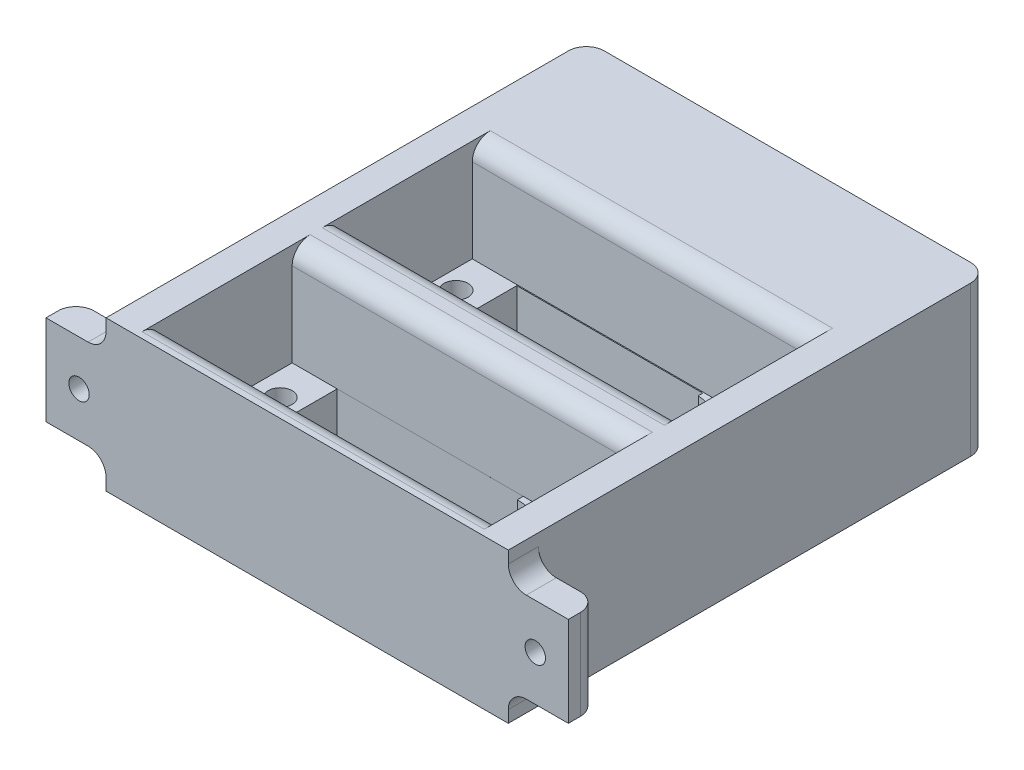
SolidWorks part; units mm, degrees
note: The reader was unsure of these and kept them because the rebuilt part matched: shared geometry of "Sketch4<2>".
ref_plane "Front Plane" through (0, 0, 0) normal (0, 0, 1) x (1, 0, 0)
ref_plane "Top Plane" through (0, 0, 0) normal (0, 1, 0) x (1, 0, 0)
ref_plane "Right Plane" through (0, 0, 0) normal (1, 0, 0) x (0, 0, -1)
sketch "Sketch1" plane through (0, 0, 0) normal (0, 1, 0) x (1, 0, 0)
  line L1 (-33.5, 15) -> (33.5, 15)
  line L2 (-33.5, 15) -> (-33.5, -15)
  line L3 (-33.5, -15) -> (33.5, -15)
  line L4 (33.5, 15) -> (33.5, -15)
  line L5 (-33.5, 15) -> (33.5, -15) construction
  line L6 (-33.5, -15) -> (33.5, 15) construction
  point P0 (0, 0)
  dimension "D1" = 67
  dimension "D2" = 30
extrude "Boss-Extrude1" add sketch "Sketch1" along normal blind 25
sketch "Sketch2" plane through (0, 25, 0) normal (0, 1, 0) x (1, 0, 0)
  line L1 (-28.5, 11) -> (28.5, 11)
  line L2 (-28.5, 11) -> (-28.5, -11)
  line L3 (-28.5, -11) -> (28.5, -11)
  line L4 (28.5, 11) -> (28.5, -11)
  line L5 (-28.5, 11) -> (28.5, -11) construction
  line L6 (-28.5, -11) -> (28.5, 11) construction
  point P0 (0, 0)
  dimension "D1" = 22
  dimension "D2" = 57
extrude "Cut-Extrude1" cut sketch "Sketch2" against normal blind 17
sketch "Sketch3" plane through (0, 8, 0) normal (0, 1, 0) x (1, 0, 0)
  line L0 (-36.7154, 0) -> (36.0411, 0) construction
  line L1 (24.5, -19.9745) -> (24.5, 16.1003) construction
  line L2 (-24.5, -21.1882) -> (-24.5, 16.1003) construction
  circle A0 centre (24.5, 5) radius 2
  circle A1 centre (24.5, -5) radius 2
  circle A2 centre (-24.5, 5) radius 2
  circle A3 centre (-24.5, -5) radius 2
  circle A4 centre (10, 0) radius 10
  circle A5 centre (-3, 0) radius 8
  dimension "D2" = 4
  dimension "D3" = 5
  dimension "D4" = 5
  dimension "D5" = 20
  dimension "D6" = 14.5
  dimension "D7" = 27.5
  dimension "D9" = 16
  dimension "D1" = 49
  dimension "D8" = 10
extrude "Cut-Extrude2" cut sketch "Sketch3" against normal up to surface (8 mm away) contours A4 A5 | A5 A4 | A2 | A3 | A0 | A1 up to face at (0, 0, 0)
sketch "Sketch4" plane through (33.5, 0, 0) normal (1, 0, 0) x (0, 0, -1)
  line L0 (-15, 25) -> (-15, 0) construction
  line L1 (-15, 20) -> (-10, 20)
  line L2 (-15, 20) -> (-15, 5)
  line L3 (-15, 5) -> (-10, 5)
  line L4 (-10, 20) -> (-10, 5)
  line L5 (-15, 20) -> (-10, 5) construction
  line L6 (-15, 5) -> (-10, 20) construction
  point P0 (-12.5, 12.5)
  dimension "D1" = 5
  dimension "D2" = 0
  dimension "D3" = 12.5
  dimension "D4" = 15
extrude "Boss-Extrude2" add sketch "Sketch4" against normal blind 10 from surface at -67 starting at face at (-33.5, 12.5, 0)
extrude "Boss-Extrude3" add sketch "Sketch4<2>" along normal blind 10
sketch "Sketch4<2>" plane through (33.5, 0, 0) normal (1, 0, 0) x (0, 0, -1) same geometry as "Sketch4"
sketch "Sketch5" plane through (0, 0, 10) normal (0, 0, -1) x (-1, 0, 0)
  circle A0 centre (38, 12.5) radius 1.7
  circle A1 centre (-38, 12.5) radius 1.7
  dimension "D1" = 3.4
  dimension "D2" = 12.5
  dimension "D3" = 38
  dimension "D4" = 38
extrude "Cut-Extrude3" cut sketch "Sketch5" against normal blind 10
sketch "Sketch6" plane through (0, 8, 0) normal (0, 1, 0) x (1, 0, 0)
  line L0 (-21, 11.0046) -> (-21.0033, -10.9975)
  line L1 (-21.0033, -10.9975) -> (10, -11.0022)
  line L3 (10, -11.0022) -> (10, 10.9978)
  line L4 (10, 10.9978) -> (-21, 11.0046)
  dimension "D1" = 31
  dimension "D2" = 22
  dimension "D3" = 11
  dimension "D4" = 10
extrude "Cut-Extrude4" cut sketch "Sketch6" against normal up to surface (8 mm away) up to face at (24.5, 0, 7)
sketch "Sketch7" plane through (0, 0, 15) normal (0, 0, 1) x (1, 0, 0)
  line L0 (7.3795, -4.5) -> (7.3795, -8.1) construction
  line L1 (-32.6205, 4.2383) -> (-210.3795, 4.2383)
  line L2 (-32.6205, 4.2383) -> (-32.6205, -6.2383)
  line L3 (-32.6205, -6.2383) -> (-210.3795, -6.2383)
  line L4 (-210.3795, 4.2383) -> (-210.3795, -6.2383)
  line L5 (-32.6205, 4.2383) -> (-210.3795, -6.2383) construction
  line L6 (-32.6205, -6.2383) -> (-210.3795, 4.2383) construction
  line L7 (-170.3795, 6.0383) -> (7.3795, 6.0383)
  line L8 (-170.3795, 6.0383) -> (-170.3795, -8.0383)
  line L9 (-170.3795, -8.0383) -> (7.3795, -8.0383)
  line L10 (7.3795, 6.0383) -> (7.3795, -8.0383)
  line L11 (-170.3795, 6.0383) -> (7.3795, -8.0383) construction
  line L12 (-170.3795, -8.0383) -> (7.3795, 6.0383) construction
  point P0 (-121.5, -1)
  point P6 (-81.5, -1)
extrude "Cut-Extrude5" [suppressed] cut sketch "Sketch7" against normal blind 2
sketch "Sketch8" plane through (0, 0, -15) normal (0, 0, -1) x (-1, 0, 0)
  line L4 (-33.5, 0) -> (33.5, 0)
  line L5 (33.5, 0) -> (33.5, 25)
  line L6 (33.5, 25) -> (-33.5, 25)
  line L8 (-33.5, 0) -> (33.5, 0)
  line L10 (33.5, 25) -> (-33.5, 25)
  line L12 (33.5, 0) -> (33.5, 25)
  line L14 (-33.5, 25) -> (-33.5, 0)
  line L15 (-33.5, 25) -> (-33.5, 0)
  dimension "D1" = 0
extrude "Boss-Extrude4" add sketch "Sketch8" along normal blind 50
sketch "Sketch9" plane through (0, 25, 0) normal (0, 1, 0) x (1, 0, 0)
  line L0 (-28.5, 41) -> (28.5, 41)
  line L1 (-28.5, 41) -> (-28.5, 19)
  line L2 (-28.5, 19) -> (28.5, 19)
  line L3 (28.5, 41) -> (28.5, 19)
  line L4 (-28.5, 41) -> (28.5, 19) construction
  line L5 (-28.5, 19) -> (28.5, 41) construction
  line L6 (-28.5, 11) -> (-28.5, -11) construction
  line L7 (28.5, -11) -> (28.5, 11) construction
  point P0 (0, 30)
  dimension "D1" = 22
  dimension "D2" = 30
extrude "Cut-Extrude6" cut sketch "Sketch9" against normal blind 17
sketch "Sketch11" plane through (0, 8, 0) normal (0, 1, 0) x (1, 0, 0)
  circle A0 centre (23.6771, 35.1212) radius 2
  circle A1 centre (23.6771, 25.1212) radius 2
  circle A2 centre (-25.3229, 35.1212) radius 2
  circle A3 centre (-25.3229, 25.1212) radius 2
  circle A4 centre (9.1771, 30.1212) radius 10
  circle A5 centre (-3.8229, 30.1212) radius 8
  dimension "D1" = 16
extrude "Cut-Extrude7" cut sketch "Sketch11" against normal through all contours A4 A5 | A5 A4 | A2 | A3 | A0 | A1
sketch "Sketch13" plane through (0, 8, 0) normal (0, 1, 0) x (1, 0, 0)
  line L0 (-20.9288, 40.8426) -> (-20.9322, 18.8406)
  line L1 (-20.9322, 18.8406) -> (10.0712, 18.8359)
  line L2 (10.0712, 18.8359) -> (10.0712, 40.8359)
  line L3 (10.0712, 40.8359) -> (-20.9288, 40.8426)
  dimension "D1" = 31
extrude "Cut-Extrude8" cut sketch "Sketch13" against normal through all
fillet "Fillet1" radius 3 12 edges at (-43.5, 12.5, 10) (43.5, 12.5, 10) (33.5, 20, 12.5) (33.5, 5, 12.5) (-33.5, 5, 12.5) (-33.5, 20, 12.5) (0, 25, -41) (0, 25, 11) (0, 25, -11) (0, 25, -19) (33.5, 12.5, -65) (-33.5, 12.5, -65)
